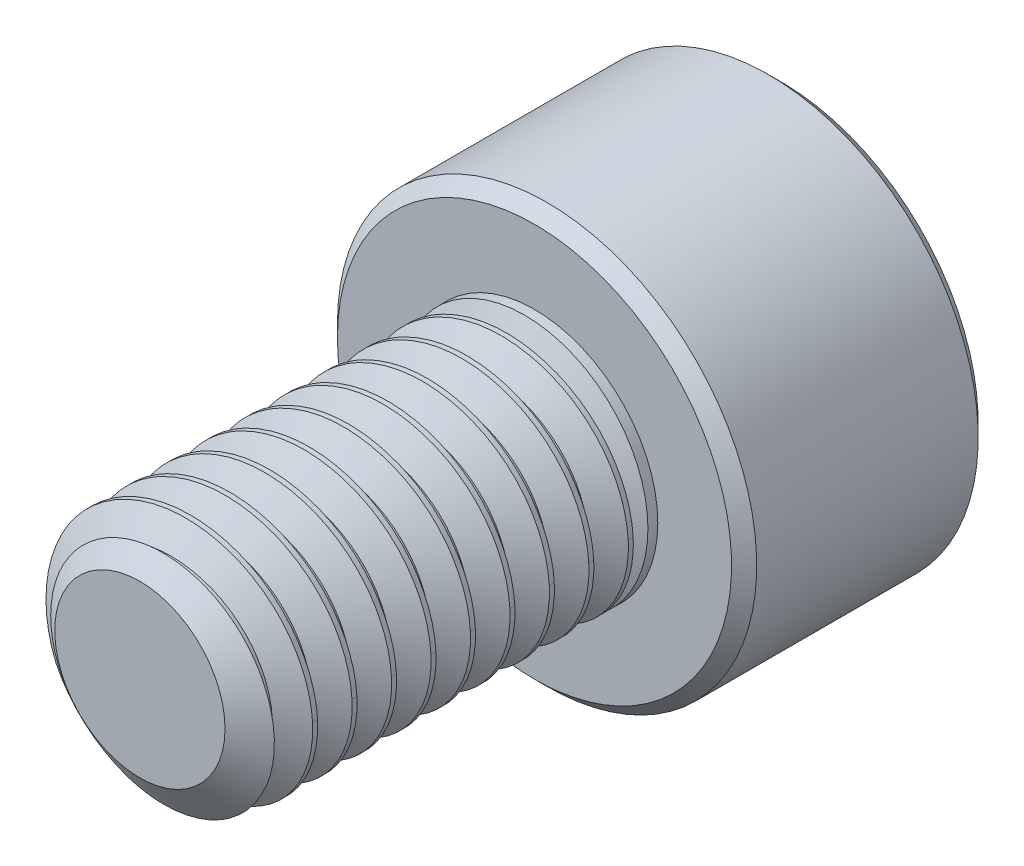
SolidWorks part; units mm, degrees
material "Alloy Steel"
ref_plane "Front Plane" through (0, 0, 0) normal (0, 0, 1) x (1, 0, 0)
ref_plane "Top Plane" through (0, 0, 0) normal (0, 1, 0) x (1, 0, 0)
ref_plane "Right Plane" through (0, 0, 0) normal (1, 0, 0) x (0, 0, -1)
sketch "Sketch1" plane through (0, 0, 0) normal (0, 0, 1) x (1, 0, 0)
  circle A0 centre (0, 0) radius 2.5
  dimension "OD" = 5
extrude "Extrude1" add sketch "Sketch1" against normal blind 8
sketch "Sketch2" plane through (0, 0, 0) normal (0, 0, 1) x (1, 0, 0)
  circle A0 centre (0, 0) radius 2.5 construction
  circle A1 centre (0, 0) radius 2.5
curve "Helix/Spiral1" pitch 0.8 height 8.8 turns 11 parameters "pitch"=0.8
sketch "Sketch3" plane through (0, 0, 0) normal (1, 0, 0) x (0, 0, -1)
  line L0 (-0.7, 2.5) -> (-0.4, 1.9804)
  line L1 (-0.4, 1.9804) -> (-0.3, 1.9804)
  line L2 (-0.3, 1.9804) -> (0, 2.5)
  line L3 (-0.7, 2.5) -> (0, 2.5)
  line L4 (-0.35, 2.5) -> (-0.35, 1.9804) construction
  line L5 (-0.55, 2.2402) -> (-0.15, 2.2402) construction
  line L6 (0, 2.5) -> (0, -2.5) construction
  line L7 (0, -2.5) -> (8, -2.5) construction
  point P11 (3.6, -2.5)
  dimension "D1" = 0.1
  dimension "D2" = 0.4
  dimension "D3" = 60
  dimension "D4" = 3.6
sweep "Cut-Sweep1" cut profiles "Sketch3" path "Helix/Spiral1"
sketch "Sketch4" plane through (0, 0, 0) normal (1, 0, 0) x (0, 0, -1)
  line L0 (0.5417, 2.5) -> (0, 1.7264)
  line L1 (0, 1.7264) -> (0, 2.5)
  line L2 (0.5417, 2.5) -> (0, 2.5)
  line L3 (-0.7, 2.5) -> (0, 2.5) construction
  line L4 (0, 0) -> (7.0209, 0) construction
  dimension "D1" = 55
  dimension "D2" = 0.254
revolve "Cut-Revolve1" cut sketch "Sketch4" angle 360 about L4
sketch "Sketch5" plane through (0, 0, 0) normal (1, 0, 0) x (0, 0, -1)
  line L0 (8, -1.991) -> (8, 1.7838) construction
  line L1 (8, 2.5) -> (0.1203, 2.5)
  line L2 (8, 2.5) -> (8, 0)
  line L3 (8, 0) -> (0.0001, 0)
  line L4 (0.0001, 2.1698) -> (0.0001, 0)
  line L5 (0.1203, 2.5) -> (0.0001, 2.1698)
  line L6 (0, 0) -> (9.9695, 0) construction
  point P3 (0.0001, 2.5)
  point P10 (0.0001, 2.5)
  dimension "D1" = 0.3302
  dimension "Thread min" = 0.0001
  dimension "D3" = 20
revolve "partially thread" [suppressed] add sketch "Sketch5" angle 360 about L6
sketch "Sketch6" plane through (0, 0, -8) normal (0, 0, -1) x (-1, 0, 0)
  circle A0 centre (0, 0) radius 4.25
  dimension "head dia" = 8.5
extrude "Extrude2" add sketch "Sketch6" along normal blind 5
sketch "Sketch7" plane through (0, 0, -13) normal (0, 0, -1) x (-1, 0, 0)
  line L1 (0, 2.3094) -> (-2, 1.1547)
  line L2 (-2, 1.1547) -> (-2, -1.1547)
  line L3 (-2, -1.1547) -> (0, -2.3094)
  line L4 (0, -2.3094) -> (2, -1.1547)
  line L5 (2, -1.1547) -> (2, 1.1547)
  line L6 (2, 1.1547) -> (0, 2.3094)
  circle A0 centre (0, 0) radius 2 construction
  dimension "hex dia" = 4
extrude "Cut-Extrude1" cut sketch "Sketch7" against normal blind 3
sketch "Sketch8" plane through (0, 0, -13) normal (0, 0, -1) x (-1, 0, 0)
  circle A0 centre (0, 0) radius 2.3094
extrude "Cut-Extrude2" cut sketch "Sketch8" against normal through all draft 45
chamfer "Chamfer1" distance 0.255 angle 45 2 edges at (-4.25, 0, -13) (-4.25, 0, -8)
sketch "Sketch9" plane through (0, 0, 0) normal (1, 0, 0) x (0, 0, -1)
  line L0 (0, 2.5) -> (0, -2.5) construction
  line L1 (4.4, 2.5) -> (4.4, -2.5) construction
  dimension "D1" = 4.4
sketch "Sketch10" plane through (0, 0, 0) normal (1, 0, 0) x (0, 0, -1)
  line L0 (8, 2.5) -> (8, 0)
  line L1 (8, 2.5) -> (7.8, 2.5)
  line L2 (7.8, 2.5) -> (6.7645, 0)
  line L3 (8, 0) -> (6.7645, 0)
  line L4 (8, 3.995) -> (8, -3.995) construction
  dimension "D1" = 22.5
  dimension "D2" = 0.2
revolve "Revolve1" add sketch "Sketch10" angle 360 about L3
equation "\"D3@Helix/Spiral1\" = \"screw length@Extrude1\"+\"pitch@Helix/Spiral1\""
equation "\"D1@Sketch3\" = \"pitch@Helix/Spiral1\"*.125"
equation "\"D2@Sketch3\" = \"pitch@Helix/Spiral1\"*.5"
equation "\"D1@Cut-Extrude1\" = \"hex dia@Sketch7\"*.75"
equation "\"D1@Chamfer1\" = \"head dia@Sketch6\"*.03"
equation "\"D1@Sketch9\" = \"pitch@Helix/Spiral1\"*5.5"
equation "\"D2@Sketch10\" = \"pitch@Helix/Spiral1\"*.25"
equation "\"D4@Sketch3\" = \"pitch@Helix/Spiral1\"*4.50"
